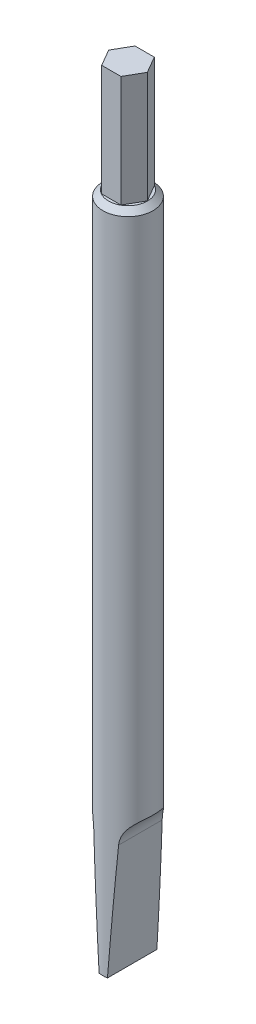
SolidWorks part; units mm, degrees
material "Cast Alloy Steel"
ref_plane "Front Plane" through (0, 0, 0) normal (0, 0, 1) x (1, 0, 0)
ref_plane "Top Plane" through (0, 0, 0) normal (0, 1, 0) x (1, 0, 0)
ref_plane "Right Plane" through (0, 0, 0) normal (1, 0, 0) x (0, 0, -1)
sketch "Sketch1" plane through (0, 0, 0) normal (0, 1, 0) x (1, 0, 0)
  line L1 (3.4641, 0) -> (1.7321, 3)
  line L2 (1.7321, 3) -> (-1.7321, 3)
  line L3 (-1.7321, 3) -> (-3.4641, 0)
  line L4 (-3.4641, 0) -> (-1.7321, -3)
  line L5 (-1.7321, -3) -> (1.7321, -3)
  line L6 (1.7321, -3) -> (3.4641, 0)
  circle A0 centre (0, 0) radius 3 construction
  circle A1 centre (0, 0) radius 3.4641
  circle A2 centre (0, 0) radius 4.5
  point P11 (0, 0)
  dimension "D2" = 9
  dimension "D1" = 6
extrude "Boss-Extrude1" add sketch "Sketch1" along normal blind 20 contours L5 L6 L1 L2 L3 L4 region at (0, 0, 0)
extrude "Boss-Extrude2" add sketch "Sketch1<3>" against normal blind 120 contours A2
sketch "Sketch1<3>" plane through (0, 0, 0) normal (0, 1, 0) x (1, 0, 0) same geometry as "Sketch1"
chamfer "Chamfer1" distance 1 angle 45 1 edges at (0, 0, 4.5)
sketch "Sketch2" plane through (0, 0, 0) normal (0, 0, 1) x (1, 0, 0)
  line L0 (0, -120) -> (0, 0) construction
  line L1 (-4.5, -120) -> (4.5, -120) construction
  line L2 (0, -120) -> (0.75, -120) construction
  line L3 (0.75, -120) -> (2.229, -98.8487)
  line L4 (-4.5, -120) -> (-0.75, -120)
  line L5 (4.5, -120) -> (4.5, -1) construction
  line L6 (4.5, -95) -> (4.5, -120)
  line L7 (4.5, -120) -> (0.75, -120)
  line L8 (-4.5, -95) -> (-4.5, -120)
  line L9 (-0.75, -120) -> (-2.229, -98.8487)
  arc A0 (2.229, -98.8487) -> (4.5, -95) centre (7.2169, -99.1975) cw
  arc A1 (-2.229, -98.8487) -> (-4.5, -95) centre (-7.2169, -99.1975) ccw
  point P9 (0.375, -120)
  dimension "D3" = 25
  dimension "D4" = 5
  dimension "D1" = 0.75
  dimension "D2" = 4
extrude "Cut-Extrude1" cut sketch "Sketch2" against normal through all both and the other way through all
